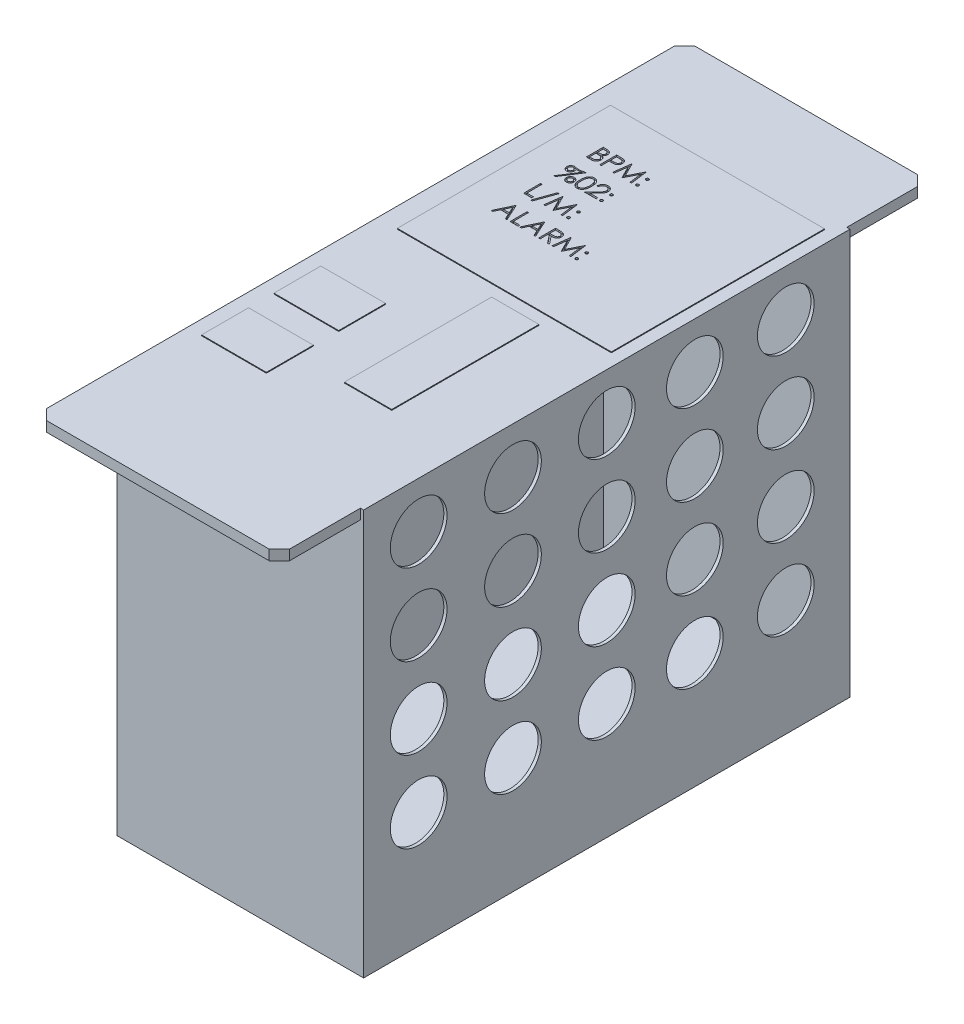
SolidWorks part; units mm, degrees
ref_plane "Front" through (0, 0, 0) normal (0, 0, 1) x (1, 0, 0)
ref_plane "Top" through (0, 0, 0) normal (0, 1, 0) x (1, 0, 0)
ref_plane "Right" through (0, 0, 0) normal (1, 0, 0) x (0, 0, -1)
ref_axis "Axis1" through (0, 0, 55) along (0, 0, -1)
sketch "Sketch1" plane through (0, 0, 0) normal (1, 0, 0) x (0, 0, -1)
  line L0 (0, 0) -> (0, 66.1792) construction
  line L1 (-76.2, 0) -> (76.2, 0)
  line L2 (76.2, 0) -> (76.2, 123.825)
  line L3 (76.2, 123.825) -> (101.6, 123.825)
  line L4 (101.6, 123.825) -> (101.6, 127)
  line L5 (101.6, 127) -> (-101.6, 127)
  line L6 (-101.6, 127) -> (-101.6, 123.825)
  line L7 (-101.6, 123.825) -> (-76.2, 123.825)
  line L8 (-76.2, 123.825) -> (-76.2, 0)
  point P6 (0, 0)
  dimension "D1" = 203.2
  dimension "D2" = 152.4
  dimension "D3" = 3.175
  dimension "D4" = 127
extrude "Boss-Extrude1" add sketch "Sketch1" against normal blind 76.2
shell "Shell1" thickness 2.54 removed face at (0, 93.6625, 0)
sketch "Sketch2" plane through (0, 0, 0) normal (1, 0, 0) x (0, 0, -1)
  line L0 (101.6, 127) -> (-101.6, 127) construction
  line L1 (-76.2, 0) -> (76.2, 0)
  line L2 (-76.2, 0) -> (-76.2, 127)
  line L3 (-76.2, 127) -> (76.2, 127)
  line L4 (76.2, 0) -> (76.2, 127)
  line L5 (76.2, 0) -> (76.2, 123.825) construction
  line L6 (-76.2, 112.5042) -> (76.2, 112.5042) construction
  line L8 (-101.6, 127) -> (-101.6, 123.825) construction
  circle A0 centre (-58.9407, 112.5042) radius 8.89
  circle A1 centre (-29.3863, 112.5042) radius 8.89
  circle A2 centre (0, 112.5042) radius 8.89
  circle A3 centre (27.5953, 112.5042) radius 8.89
  circle A4 centre (56.0906, 112.5042) radius 8.89
  circle A5 centre (-58.9407, 87.1042) radius 8.89
  circle A6 centre (-29.3863, 87.1042) radius 8.89
  circle A7 centre (0, 87.1042) radius 8.89
  circle A8 centre (27.5953, 87.1042) radius 8.89
  circle A9 centre (56.0906, 87.1042) radius 8.89
  circle A10 centre (-58.9407, 61.7042) radius 8.89
  circle A11 centre (-29.3863, 61.7042) radius 8.89
  circle A12 centre (0, 61.7042) radius 8.89
  circle A13 centre (27.5953, 61.7042) radius 8.89
  circle A14 centre (56.0906, 61.7042) radius 8.89
  circle A15 centre (-58.9407, 36.3042) radius 8.89
  circle A16 centre (-29.3863, 36.3042) radius 8.89
  circle A17 centre (0, 36.3042) radius 8.89
  circle A18 centre (27.5953, 36.3042) radius 8.89
  circle A19 centre (56.0906, 36.3042) radius 8.89
  dimension "D1" = 17.78
  dimension "D2" = 42.6593
  dimension "D3" = 72.2137
  dimension "D4" = 129.1953
  dimension "D5" = 157.6906
  dimension "D6" = 14.4958
  dimension "D8" = 25.4
  dimension "D9" = 203.2
  dimension "D7" = 4
extrude "Boss-Extrude2" add sketch "Sketch2" along normal blind 1
sketch "Sketch3" plane through (0, 127, 0) normal (0, 1, 0) x (1, 0, 0)
  line L0 (0, 101.6) -> (0, 76.2) construction
  line L8 (-69.9012, 72.0727) -> (-2.8379, 72.0727)
  line L9 (-69.9012, 72.0727) -> (-69.9012, 5.2728)
  line L14 (-69.9012, 5.2728) -> (-2.8379, 5.2728)
  line L15 (-2.8379, 72.0727) -> (-2.8379, 5.2728)
  line L20 (-69.9012, 72.0727) -> (-2.8379, 5.2728) construction
  line L21 (-69.9012, 5.2728) -> (-2.8379, 72.0727) construction
  line L26 (-71.6493, -16.9526) -> (-51.3469, -16.9526)
  line L27 (-71.6493, -16.9526) -> (-71.6493, -31.651)
  line L32 (-71.6493, -31.651) -> (-51.3469, -31.651)
  line L33 (-51.3469, -16.9526) -> (-51.3469, -31.651)
  line L38 (-71.6493, -16.9526) -> (-51.3469, -31.651) construction
  line L39 (-71.6493, -31.651) -> (-51.3469, -16.9526) construction
  line L40 (-36.4758, 1.3918) -> (-21.6307, 1.3918)
  line L41 (-36.4758, 1.3918) -> (-36.4758, -44.7593)
  line L42 (-36.4758, -44.7593) -> (-21.6307, -44.7593)
  line L43 (-21.6307, 1.3918) -> (-21.6307, -44.7593)
  line L44 (-36.4758, 1.3918) -> (-21.6307, -44.7593) construction
  line L45 (-36.4758, -44.7593) -> (-21.6307, 1.3918) construction
  line L46 (-71.6493, -39.5967) -> (-51.3469, -39.5967)
  line L47 (-71.6493, -39.5967) -> (-71.6493, -54.3179)
  line L48 (-71.6493, -54.3179) -> (-51.3469, -54.3179)
  line L49 (-51.3469, -39.5967) -> (-51.3469, -54.3179)
  line L50 (-71.6493, -39.5967) -> (-51.3469, -54.3179) construction
  line L51 (-71.6493, -54.3179) -> (-51.3469, -39.5967) construction
  point P0 (-36.3696, 38.6727)
  point P5 (-29.0532, -21.6837)
  point P7 (-61.4981, -24.3018)
  point P15 (-61.4981, -46.9573)
  dimension "D3" = 29.0532
  dimension "D4" = 36.3696
  dimension "D1" = 2.8379
  dimension "D2" = 21.6307
  dimension "D5" = 51.3469
  dimension "D6" = 61.4981
  dimension "D7" = 47.2821
  dimension "D8" = 54.6427
  dimension "D9" = 56.8407
  dimension "D10" = 69.949
  dimension "D11" = 77.2982
  dimension "D12" = 79.9163
  dimension "D13" = 106.8728
  dimension "D14" = 140.2727
extrude "Boss-Extrude3" add sketch "Sketch3" along normal blind 0.254
chamfer "Chamfer1" distance 3.175 angle 45 4 edges at (0, 125.4125, 101.6) (-76.2, 125.4125, 101.6) (-76.2, 125.4125, -101.6) (0, 125.4125, -101.6)
sketch "Sketch4" plane through (0, 127.254, 0) normal (0, 1, 0) x (1, 0, 0)
  text T0 "BPM:\r\n%02:\r\nL/M:\r\nALARM:\r\n" font "Century Gothic" height in points 20
extrude "Cut-Extrude1" cut sketch "Sketch4" against normal blind 0.508
